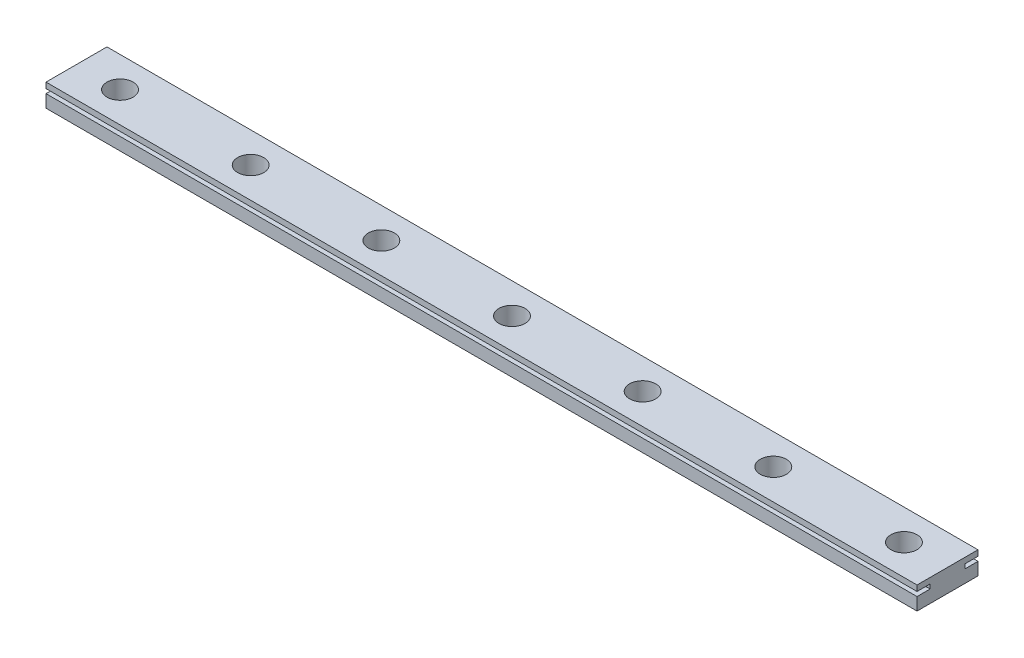
SolidWorks part; units mm, degrees
ref_plane "前视基准面" through (0, 0, 0) normal (0, 0, 1) x (1, 0, 0)
ref_plane "上视基准面" through (0, 0, 0) normal (0, 1, 0) x (1, 0, 0)
ref_plane "右视基准面" through (0, 0, 0) normal (1, 0, 0) x (0, 0, -1)
sketch "草图1" plane through (0, 0, 0) normal (0, 1, 0) x (1, 0, 0)
  line L1 (0, 0) -> (200, 0)
  line L2 (0, 0) -> (0, 14)
  line L3 (0, 14) -> (200, 14)
  line L4 (200, 0) -> (200, 14)
  dimension "D1" = 14
  dimension "D2" = 200
extrude "凸台-拉伸1" add sketch "草图1" along normal blind 5.2
sketch "草图2" plane through (0, 0, 0) normal (-1, 0, 0) x (0, 0, 1)
  line L0 (-14, 2.9) -> (-11, 2.9)
  line L1 (-14, 5.2) -> (-14, 0) construction
  line L2 (-11, 2.9) -> (-11, 3.9)
  line L3 (-11, 3.9) -> (-14, 3.9)
  line L4 (-14, 3.9) -> (-14, 2.9)
  line L5 (-14, 0) -> (0, 0) construction
  line L6 (-7, 5.2) -> (-7, 0) construction
  line L7 (-14, 5.2) -> (0, 5.2) construction
  line L8 (-3, 3.9) -> (0, 3.9)
  line L9 (-3, 2.9) -> (-3, 3.9)
  line L10 (0, 2.9) -> (-3, 2.9)
  line L11 (0, 3.9) -> (0, 2.9)
  dimension "D1" = 2.9
  dimension "D2" = 1
  dimension "D3" = 3
extrude "切除-拉伸1" cut sketch "草图2" against normal blind 210
sketch "草图3" plane through (0, 5.2, 0) normal (0, 1, 0) x (1, 0, 0)
  line L0 (0, 7) -> (200, 7) construction
  line L1 (0, 14) -> (0, 0) construction
  line L2 (200, 0) -> (200, 14) construction
  circle A0 centre (10, 7) radius 3
  circle A1 centre (10, 7) radius 1.75
  dimension "D1" = 6
  dimension "D2" = 3.5
  dimension "D3" = 10
extrude "切除-拉伸2" cut sketch "草图3" against normal blind 31 contours A1
extrude "切除-拉伸3" cut sketch "草图3<3>" against normal blind 4.5 contours A1 L0 | L0 A1 | A0 region at (10, 5.2, -6.2573) region at (10, 5.2, -7.7427)
sketch "草图3<3>" plane through (0, 5.2, 0) normal (0, 1, 0) x (1, 0, 0) same geometry as "草图3"
pattern_linear "阵列(线性)1" count 7 spacing 30 along (1, 0, 0) of "切除-拉伸3", "切除-拉伸2"
